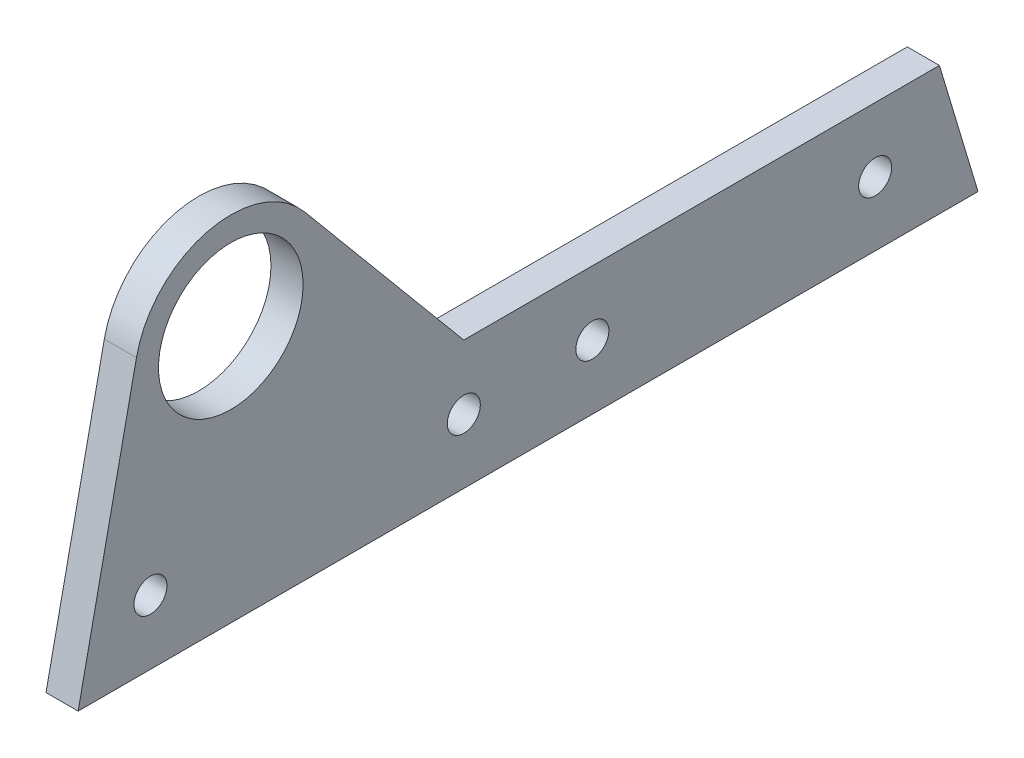
SolidWorks part; units mm, degrees
material "PC High Viscosity"
ref_plane "Front Plane" through (0, 0, 0) normal (0, 0, 1) x (1, 0, 0)
ref_plane "Top Plane" through (0, 0, 0) normal (0, 1, 0) x (1, 0, 0)
ref_plane "Right Plane" through (0, 0, 0) normal (1, 0, 0) x (0, 0, -1)
sketch "Sketch1" plane through (0, 0, 0) normal (1, 0, 0) x (0, 0, -1)
  line L0 (0, 0) -> (-58.7375, 0) construction
  line L1 (-58.7375, 0) -> (-58.7375, 38.1) construction
  line L2 (0, 0) -> (12.7, 0) construction
  line L3 (-12.7, 0) -> (-12.7, -12.7) construction
  line L4 (-88.9, -961.9) -> (-88.9, 49038.1) construction
  line L5 (-12.7, -12.7) -> (-88.9, -12.7)
  line L6 (-88.9, -12.7) -> (-77.3789, 42.0246)
  line L7 (-12.7, 0) -> (-12.7, 12.7) construction
  line L8 (-12.7, 12.7) -> (-44.1169, 50.3123)
  line L9 (-12.7, 12.7) -> (25.4, 12.7)
  line L10 (-12.7, -12.7) -> (25.4, -12.7)
  line L12 (-1058.7375, 38.1) -> (48941.2625, 38.1) construction
  line L13 (-56.4955, 38.916) -> (46928.1355, 17139.9232) construction
  line L15 (25.4, -12.7) -> (88.9, -12.7)
  line L16 (88.9, -12.7) -> (81.28, 12.7)
  line L17 (25.4, 12.7) -> (81.28, 12.7)
  line L18 (-58.7375, 0) -> (-74.6125, 0) construction
  line L19 (12.7, 0) -> (68.58, 0) construction
  circle A0 centre (-58.7375, 38.1) radius 14.2875
  circle A1 centre (-12.7, 0) radius 3.2639
  circle A2 centre (12.7, 0) radius 3.2639
  arc A3 (-44.1169, 50.3123) -> (-77.3789, 42.0246) centre (-58.7375, 38.1) ccw
  circle A6 centre (-74.6125, 0) radius 3.2639
  circle A7 centre (68.58, 0) radius 3.2639
  point P5 (-12.7, 0)
  point P12 (162.0433, 118.4576)
  dimension "D3" = 28.575
  dimension "D6" = 6.5278
  dimension "D7" = 6.5278
  dimension "D9" = 38.1
  dimension "D14" = 6.5278
  dimension "D15" = 55.88
  dimension "D18" = 6.5278
  dimension "D1" = 58.7375
  dimension "D2" = 38.1
  dimension "D4" = 12.7
  dimension "D5" = 12.7
  dimension "D8" = 12.7
  dimension "D10" = 12.7
  dimension "D11" = 38.1
  dimension "D12" = 20
  dimension "D13" = 15.875
  dimension "D16" = 63.5
  dimension "D17" = 76.2
  dimension "D19" = 12.7
extrude "Boss-Extrude1" add sketch "Sketch1" along normal blind 6.35
